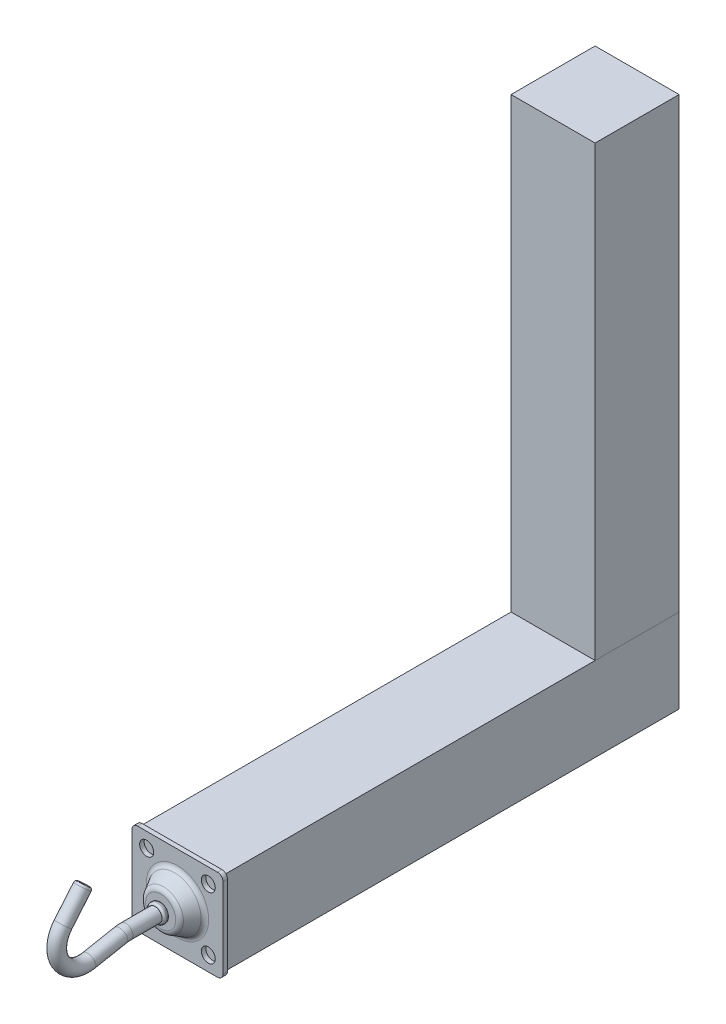
SolidWorks part; units mm, degrees
ref_plane "Front" through (0, 0, 0) normal (0, 0, 1) x (1, 0, 0)
ref_plane "Top" through (0, 0, 0) normal (0, 1, 0) x (1, 0, 0)
ref_plane "Right" through (0, 0, 0) normal (1, 0, 0) x (0, 0, -1)
sketch "Sketch1" plane through (0, 0, 0) normal (0, 0, 1) x (1, 0, 0)
  line L1 (-20.6375, 20.6375) -> (20.6375, 20.6375)
  line L2 (-20.6375, 20.6375) -> (-20.6375, -20.6375)
  line L3 (-20.6375, -20.6375) -> (20.6375, -20.6375)
  line L4 (20.6375, 20.6375) -> (20.6375, -20.6375)
  line L5 (-20.6375, 20.6375) -> (20.6375, -20.6375) construction
  line L6 (-20.6375, -20.6375) -> (20.6375, 20.6375) construction
  point P0 (0, 0)
  dimension "D1" = 41.275
extrude "Boss-Extrude1" add sketch "Sketch1" along normal blind 2.032
sketch "Sketch2" plane through (0, 0, 2.032) normal (0, 0, 1) x (1, 0, 0)
  circle A0 centre (0, 0) radius 12.7
  dimension "D1" = 25.4
extrude "Boss-Extrude2" add sketch "Sketch2" along normal blind 7.62 draft 30
fillet "Fillet3" radius 2.54 2 edges at (12.7, 0, 2.032) (8.3006, 0, 9.652)
shell "Shell1" thickness 2.032 removed face at (0, 0, 0)
fillet "Fillet1" radius 2.54 4 edges at (20.6375, -20.6375, 1.016) (-20.6375, -20.6375, 1.016) (-20.6375, 20.6375, 1.016) (20.6375, 20.6375, 1.016)
sketch "Sketch3" plane through (0, 0, 9.652) normal (0, 0, 1) x (1, 0, 0)
  circle A0 centre (0, 0) radius 4.1275
  dimension "D1" = 8.255
extrude "Boss-Extrude3" add sketch "Sketch3" along normal blind 2.54 separate body
sketch "Sketch4" plane through (0, 0, 0) normal (1, 0, 0) x (0, 0, -1)
  line L0 (-12.192, 0) -> (-25.4, 0)
  line L1 (-12.192, 4.1275) -> (-12.192, -4.1275) construction
  line L2 (-27.7654, -0.2222) -> (-42.209, -2.9602)
  line L3 (-44.495, 28.194) -> (-53.8974, 16.9886)
  line L4 (-52.7149, -3.175) -> (-41.9923, -3.175) construction
  line L5 (-44.495, 28.194) -> (-44.495, -3.175) construction
  arc A0 (-53.8974, 16.9886) -> (-42.209, -2.9602) centre (-44.495, 9.099) ccw
  arc A1 (-25.4, 0) -> (-27.7654, -0.2222) centre (-25.4, -12.7) ccw
  circle A2 centre (-44.495, 28.194) radius 3.556 construction
  circle A3 centre (-56.769, 9.099) radius 3.556 construction
  dimension "D1" = 12.7
  dimension "D3" = 7.112
  dimension "D4" = 60.325
  dimension "D7" = 31.75
  dimension "D2" = 25.4
  dimension "D5" = 3.175
  dimension "D6" = 50
fillet "Fillet4" radius 1.016 2 edges at (4.1275, 0, 9.652) (4.1275, 0, 12.192)
combine bodies "Combine1" operation type add bodies to combine 110 111
sketch "Sketch5" plane through (0, 0, 12.192) normal (0, 0, 1) x (1, 0, 0)
  circle A0 centre (0, 0) radius 3.175
  dimension "D1" = 6.35
sweep "Sweep1" add profiles "Sketch5" path "Sketch4"
fillet "Fillet2" radius 1.016 1 edges at (3.175, 28.194, 44.495)
sketch "Sketch6" plane through (0, 0, 2.032) normal (0, 0, 1) x (1, 0, 0)
  line L1 (-13.97, -13.97) -> (13.97, -13.97) construction
  line L2 (-13.97, -13.97) -> (-13.97, 13.97) construction
  line L3 (-13.97, 13.97) -> (13.97, 13.97) construction
  line L4 (13.97, -13.97) -> (13.97, 13.97) construction
  line L5 (-13.97, -13.97) -> (13.97, 13.97) construction
  line L6 (-13.97, 13.97) -> (13.97, -13.97) construction
  circle A0 centre (-13.97, -13.97) radius 3.175
  circle A1 centre (13.97, -13.97) radius 3.175
  circle A2 centre (13.97, 13.97) radius 3.175
  circle A3 centre (-13.97, 13.97) radius 3.175
  point P0 (0, 0)
  dimension "D2" = 6.35
  dimension "D1" = 27.94
extrude "Cut-Extrude1" cut sketch "Sketch6" against normal up to surface (2.032 mm away) up to face at (0, 0, 0)
sketch "Sketch7" plane through (0, 0, 0) normal (0, 0, -1) x (-1, 0, 0)
  line L1 (-19.05, 19.05) -> (19.05, 19.05)
  line L2 (-19.05, 19.05) -> (-19.05, -19.05)
  line L3 (-19.05, -19.05) -> (19.05, -19.05)
  line L4 (19.05, 19.05) -> (19.05, -19.05)
  line L5 (-19.05, 19.05) -> (19.05, -19.05) construction
  line L6 (-19.05, -19.05) -> (19.05, 19.05) construction
  point P0 (0, 0)
  dimension "D1" = 38.1
  dimension "D2" = 38.1
extrude "Boss-Extrude4" add sketch "Sketch7" along normal blind 206.375 separate body
sketch "Sketch9" plane through (0, 19.05, 0) normal (0, 1, 0) x (1, 0, 0)
  line L0 (-19.05, 206.375) -> (-19.05, 0) construction
  line L1 (19.05, 206.375) -> (-19.05, 206.375)
  line L2 (19.05, 206.375) -> (19.05, 168.275)
  line L3 (19.05, 168.275) -> (-19.05, 168.275)
  line L4 (-19.05, 206.375) -> (-19.05, 168.275)
extrude "Boss-Extrude5" add sketch "Sketch9" along normal blind 203.2 separate body
